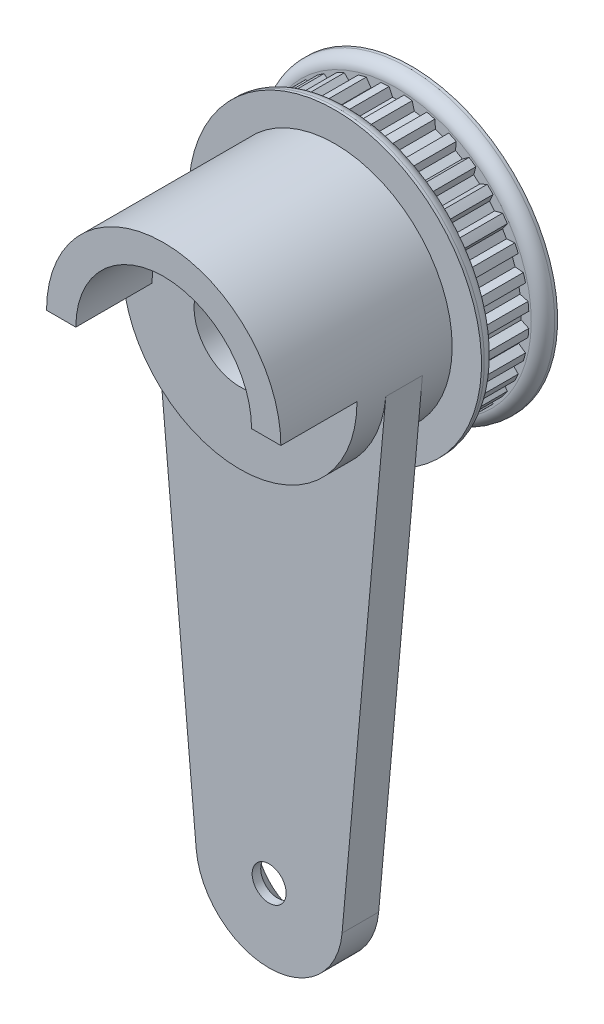
SolidWorks part; units mm, degrees
ref_plane "Front" through (0, 0, 0) normal (0, 0, 1) x (1, 0, 0)
ref_plane "Top" through (0, 0, 0) normal (0, 1, 0) x (1, 0, 0)
ref_plane "Right" through (0, 0, 0) normal (1, 0, 0) x (0, 0, -1)
sketch "Sketch1" plane through (0, 0, 0) normal (0, 0, 1) x (1, 0, 0)
  line L0 (-254, 0) -> (254, 0) construction
  circle A0 centre (0, 0) radius 13.97
  circle A1 centre (0, 0) radius 12.7 construction
  circle A3 centre (0, 0) radius 11.2306 construction
  dimension "D1" = 1.4694
  dimension "D2" = 2.7394
  dimension "D3" = 1.27
extrude "Boss-Extrude1" add sketch "Sketch1" against normal blind 12.7
sketch "Sketch2" plane through (0, 0, 0) normal (1, 0, 0) x (0, 0, -1)
  line L0 (12.7, 0) -> (23.876, 0)
  line L1 (12.7, 0) -> (12.7, 10.668)
  line L2 (12.7, 10.668) -> (23.876, 10.668)
  line L3 (23.876, 10.668) -> (23.876, 0)
  point P5 (23.876, -10.668)
  point P6 (0, -13.97)
  point P7 (12.7, -13.97)
  point P9 (0, 13.97)
revolve "Revolve1" add sketch "Sketch2" angle 360 mid plane about L0 other way angle 360
fillet "Fillet2" radius 0.2794 3 edges at (13.97, 0, -12.7) (13.97, 0, 0) (10.668, 0, -12.7)
sketch "Sketch3" plane through (0, 0, 0) normal (0, 0, 1) x (1, 0, 0)
  line L0 (0, 0) -> (0, 13.97) construction
  line L1 (-4.0817, 11.2144) -> (0, 12.7)
  line L2 (-9.5921, 12.7) -> (9.5921, 12.7) construction
  line L3 (-9.0136, 9.4193) -> (9.0136, 15.9807) construction
  line L4 (-4.0817, 11.2144) -> (0, 0) construction
  line L5 (-9.951, 6.5878) -> (0, 0) construction
  line L6 (-9.951, 6.5878) -> (-3.3571, 16.548) construction
  line L7 (-2.8353, 11.5924) -> (0, 0) construction
  line L8 (-2.8353, 11.5924) -> (0.1182, 12.3148) construction
  arc A0 (-4.0817, 11.2144) -> (-9.951, 6.5878) centre (0, 0) ccw
  circle A1 centre (0, 0) radius 12.7 construction
  circle A2 centre (0, 0) radius 11.9341 construction
  arc A3 (-4.0817, 11.2144) -> (-2.8353, 11.5924) centre (0, 0) cw
  circle A4 centre (0, 0) radius 13.97 construction
  point P6 (0, 12.7)
  dimension "D1" = 4.3437
  dimension "D3" = 11.9451
  dimension "D5" = 3.0406
  dimension "D2" = 7.6014
  dimension "D4" = 1.3031
sketch "Sketch4" plane through (0, 0, 0) normal (0, 0, 1) x (1, 0, 0)
  line L0 (0, 0) -> (0.9934, 12.6218) construction
  line L1 (0.2108, 11.9322) -> (0.2108, 11.2286)
  line L2 (0, 12.7) -> (1.9867, 12.5436) construction
  line L3 (1.6584, 11.8183) -> (1.5483, 11.1234)
  line L4 (0.2108, 11.2286) -> (0, 0) construction
  line L5 (0, 0) -> (0, 13.97) construction
  line L6 (-9.951, 6.5878) -> (-3.3571, 16.548) construction
  line L7 (-9.951, 6.5878) -> (-3.3571, 16.548) construction
  arc A0 (1.5483, 11.1234) -> (0.2108, 11.2286) centre (0, 0) ccw
  arc A1 (0, 12.7) -> (1.9867, 12.5436) centre (0, 0) cw construction
  circle A2 centre (0, 0) radius 12.7 construction
  circle A3 centre (0, 0) radius 11.9341 construction
  circle A4 centre (0, 0) radius 11.2306 construction
  arc A5 (5.9045, 15.8191) -> (-3.3571, 16.548) centre (0, 0) ccw
  spline S0 degree 2 poles (-3.3571, 16.548) (-0.4015, 14.8243) (0.2108, 11.9322) knots 0 0 0 1 1 1
  spline S1 degree 2 poles (5.9045, 15.8191) (2.7156, 14.579) (1.6584, 11.8183) knots 0 0 0 1 1 1
  dimension "D1" = 1.9949
extrude "Cut-Extrude1" cut sketch "Sketch4" against normal through all
fillet "Fillet1" radius 0.5985 2 edges at (1.5483, 11.1234, -6.35) (0.2108, 11.2286, -6.35)
pattern_circular "CirPattern1" count 20 over 360 about axis through (0, 0, -12.7) along (0, 0, 1) of "Cut-Extrude1", "Fillet1"
sketch "Sketch5" plane through (0, 0, 0) normal (0, 0, 1) x (1, 0, 0)
  circle A0 centre (0, 0) radius 6.35
  circle A1 centre (0, 0) radius 6.35 construction
  dimension "Bore Min" = 12.7
  dimension "Bore Max" = 12.7
extrude "Cut-Extrude2" cut sketch "Sketch5" against normal through all
chamfer "Chamfer1" distance 0.5334 angle 45 3 edges at (10.668, 0, -23.876) (6.35, 0, 0) (6.35, 0, -23.876)
sketch "Pitch Dia" plane through (0, 0, 0) normal (0, 0, 1) x (1, 0, 0)
  circle A0 centre (0, 0) radius 12.7 construction
  circle A1 centre (0, 0) radius 12.7 construction
sketch "Sketch7" plane through (0, 0, 0) normal (0, 0, 1) x (1, 0, 0)
  circle A0 centre (0, 0) radius 15.875
  dimension "D1" = 31.75
extrude "Cut-Extrude6" cut sketch "Sketch7" against normal blind 2.54
sketch "Sketch6" plane through (0, 0, -23.876) normal (0, 0, -1) x (-1, 0, 0)
  circle A0 centre (0, 0) radius 15.875
  dimension "D1" = 31.75
extrude "Cut-Extrude7" cut sketch "Sketch6" against normal offset from surface (16.5735 mm away) 4.7625 up to face at (6.35, 0, -2.54)
sketch "Sketch9" plane through (0, 0, -2.54) normal (0, 0, 1) x (1, 0, 0)
  circle A0 centre (0, 0) radius 6.35
  circle A1 centre (0, 0) radius 3.9688
  circle A2 centre (0, 0) radius 6.35 construction
  dimension "D1" = 7.9375
extrude "Boss-Extrude3" add sketch "Sketch9" against normal up to surface (4.7625 mm away) up to face at (6.35, 0, -7.3025)
sketch "Sketch8" plane through (0, 0, -2.54) normal (0, 0, 1) x (1, 0, 0)
  line L0 (10.1192, -0.9099) -> (6.3245, -43.1137)
  line L1 (-6.3245, -43.1137) -> (-10.1192, -0.9099)
  line L2 (0, -42.545) -> (0, 0) construction
  arc A0 (-10.1192, -0.9099) -> (10.1192, -0.9099) centre (0, 0) cw
  arc A1 (6.3245, -43.1137) -> (-6.3245, -43.1137) centre (0, -42.545) cw
  circle A2 centre (0, -42.545) radius 1.4732 construction
  circle A3 centre (0, 0) radius 3.9688
  circle A4 centre (0, 0) radius 3.9688 construction
  dimension "D1" = 10.16
  dimension "D3" = 2.9464
  dimension "D4" = 6.35
  dimension "D2" = 42.545
extrude "Boss-Extrude2" add sketch "Sketch8" along normal blind 3.175
sketch "Sketch10" plane through (0, 0, 0.635) normal (0, 0, 1) x (1, 0, 0)
  circle A0 centre (0, 0) radius 10.16
  circle A1 centre (0, 0) radius 3.9688
  circle A2 centre (0, 0) radius 3.9688 construction
  arc A3 (10.1192, -0.9099) -> (-10.1192, -0.9099) centre (0, 0) ccw construction
extrude "Boss-Extrude4" add sketch "Sketch10" along normal blind 2.54
sketch "Sketch12" plane through (0, 0, 3.175) normal (0, 0, 1) x (1, 0, 0)
  line L0 (-10.16, 0) -> (-7.62, 0)
  line L1 (7.62, 0) -> (10.16, 0)
  arc A0 (-10.16, 0) -> (10.16, 0) centre (0, 0) cw
  circle A2 centre (0, 0) radius 10.16 construction
  arc A3 (10.1192, -0.9099) -> (-10.1192, -0.9099) centre (0, 0) ccw construction
  arc A4 (-7.62, 0) -> (7.62, 0) centre (0, 0) cw
  dimension "D1" = 2.54
extrude "Boss-Extrude5" add sketch "Sketch12" along normal blind 6.604
sketch "Sketch13" plane through (0, 0, -7.3025) normal (0, 0, -1) x (-1, 0, 0)
  circle A0 centre (0, 0) radius 15.875
  dimension "D1" = 31.75
extrude "Cut-Extrude8" cut sketch "Sketch13" against normal up to surface (4.7625 mm away) up to face at (-0.6308, -12.5539, -2.54)
sketch "Sketch18" plane through (0, 0, -2.54) normal (0, 0, -1) x (-1, 0, 0)
  circle A0 centre (0, 0) radius 10.16
  arc A1 (10.1192, -0.9099) -> (-10.1192, -0.9099) centre (0, 0) ccw construction
  circle A2 centre (0, 0) radius 3.9688
  circle A3 centre (0, 0) radius 3.9688 construction
extrude "Boss-Extrude10" add sketch "Sketch18" along normal blind 2.54
sketch "Sketch16" plane through (0, 0, -5.08) normal (0, 0, -1) x (-1, 0, 0)
  circle A0 centre (0, 0) radius 12.7
  circle A1 centre (0, 0) radius 3.9688
  circle A2 centre (0, 0) radius 3.9688 construction
  dimension "D1" = 25.4
extrude "Boss-Extrude8" add sketch "Sketch16" along normal blind 1.27
sketch "Sketch14" plane through (0, 0, -6.35) normal (0, 0, -1) x (-1, 0, 0)
  line L120 (10.5919, 2.2117) -> (10.7096, 1.5443)
  line L121 (11.1831, 2.6256) -> (10.5919, 2.2117)
  line L122 (10.2788, 3.3805) -> (10.9976, 3.3177)
  line L123 (10.047, 4.0174) -> (10.2788, 3.3805)
  line L124 (10.5572, 4.5277) -> (10.047, 4.0174)
  line L125 (9.5356, 5.1141) -> (10.2544, 5.177)
  line L126 (9.1967, 5.701) -> (9.5356, 5.1141)
  line L127 (9.6106, 6.2921) -> (9.1967, 5.701)
  line L128 (8.5027, 6.6922) -> (9.1997, 6.879)
  line L129 (8.067, 7.2114) -> (8.5027, 6.6922)
  line L130 (8.372, 7.8654) -> (8.067, 7.2114)
  line L131 (7.2114, 8.067) -> (7.8654, 8.372)
  line L132 (6.6922, 8.5027) -> (7.2114, 8.067)
  line L133 (6.879, 9.1997) -> (6.6922, 8.5027)
  line L134 (5.701, 9.1967) -> (6.2921, 9.6106)
  line L135 (5.1141, 9.5356) -> (5.701, 9.1967)
  line L136 (5.177, 10.2544) -> (5.1141, 9.5356)
  line L137 (4.0174, 10.047) -> (4.5277, 10.5572)
  line L138 (3.3805, 10.2788) -> (4.0174, 10.047)
  line L139 (3.3177, 10.9976) -> (3.3805, 10.2788)
  line L140 (2.2117, 10.5919) -> (2.6256, 11.1831)
  line L141 (1.5443, 10.7096) -> (2.2117, 10.5919)
  line L142 (1.3575, 11.4067) -> (1.5443, 10.7096)
  line L143 (0.3389, 10.8151) -> (0.6438, 11.4691)
  line L144 (-0.3389, 10.8151) -> (0.3389, 10.8151)
  line L145 (-0.6438, 11.4691) -> (-0.3389, 10.8151)
  line L146 (-1.5443, 10.7096) -> (-1.3575, 11.4067)
  line L147 (-2.2117, 10.5919) -> (-1.5443, 10.7096)
  line L148 (-2.6256, 11.1831) -> (-2.2117, 10.5919)
  line L149 (-3.3805, 10.2788) -> (-3.3177, 10.9976)
  line L150 (-4.0174, 10.047) -> (-3.3805, 10.2788)
  line L151 (-4.5277, 10.5572) -> (-4.0174, 10.047)
  line L152 (-5.1141, 9.5356) -> (-5.177, 10.2544)
  line L153 (-5.701, 9.1967) -> (-5.1141, 9.5356)
  line L154 (-6.2921, 9.6106) -> (-5.701, 9.1967)
  line L155 (-6.6922, 8.5027) -> (-6.879, 9.1997)
  line L156 (-7.2114, 8.067) -> (-6.6922, 8.5027)
  line L157 (-7.8654, 8.372) -> (-7.2114, 8.067)
  line L158 (-8.067, 7.2114) -> (-8.372, 7.8654)
  line L159 (-8.5027, 6.6922) -> (-8.067, 7.2114)
  line L160 (-9.1997, 6.879) -> (-8.5027, 6.6922)
  line L161 (-9.1967, 5.701) -> (-9.6106, 6.2921)
  line L162 (-9.5356, 5.1141) -> (-9.1967, 5.701)
  line L163 (-10.2544, 5.177) -> (-9.5356, 5.1141)
  line L164 (-10.047, 4.0174) -> (-10.5572, 4.5277)
  line L165 (-10.2788, 3.3805) -> (-10.047, 4.0174)
  line L166 (-10.9976, 3.3177) -> (-10.2788, 3.3805)
  line L167 (-10.5919, 2.2117) -> (-11.1831, 2.6256)
  line L168 (-10.7096, 1.5443) -> (-10.5919, 2.2117)
  line L169 (-11.4067, 1.3575) -> (-10.7096, 1.5443)
  line L170 (-10.8151, 0.3389) -> (-11.4691, 0.6438)
  line L171 (-10.8151, -0.3389) -> (-10.8151, 0.3389)
  line L172 (-11.4691, -0.6438) -> (-10.8151, -0.3389)
  line L173 (-10.7096, -1.5443) -> (-11.4067, -1.3575)
  line L174 (-10.5919, -2.2117) -> (-10.7096, -1.5443)
  line L175 (-11.1831, -2.6256) -> (-10.5919, -2.2117)
  line L176 (-10.2788, -3.3805) -> (-10.9976, -3.3177)
  line L177 (-10.047, -4.0174) -> (-10.2788, -3.3805)
  line L178 (-10.5572, -4.5277) -> (-10.047, -4.0174)
  line L179 (-9.5356, -5.1141) -> (-10.2544, -5.177)
  line L180 (-9.1967, -5.701) -> (-9.5356, -5.1141)
  line L181 (-9.6106, -6.2921) -> (-9.1967, -5.701)
  line L182 (-8.5027, -6.6922) -> (-9.1997, -6.879)
  line L183 (-8.067, -7.2114) -> (-8.5027, -6.6922)
  line L184 (-8.372, -7.8654) -> (-8.067, -7.2114)
  line L185 (-7.2114, -8.067) -> (-7.8654, -8.372)
  line L186 (-6.6922, -8.5027) -> (-7.2114, -8.067)
  line L187 (-6.879, -9.1997) -> (-6.6922, -8.5027)
  line L188 (-5.701, -9.1967) -> (-6.2921, -9.6106)
  line L189 (-5.1141, -9.5356) -> (-5.701, -9.1967)
  line L190 (-5.177, -10.2544) -> (-5.1141, -9.5356)
  line L191 (-4.0174, -10.047) -> (-4.5277, -10.5572)
  line L192 (-3.3805, -10.2788) -> (-4.0174, -10.047)
  line L193 (-3.3177, -10.9976) -> (-3.3805, -10.2788)
  line L194 (-2.2117, -10.5919) -> (-2.6256, -11.1831)
  line L195 (-1.5443, -10.7096) -> (-2.2117, -10.5919)
  line L196 (-1.3575, -11.4067) -> (-1.5443, -10.7096)
  line L197 (-0.3389, -10.8151) -> (-0.6438, -11.4691)
  line L198 (0.3389, -10.8151) -> (-0.3389, -10.8151)
  line L199 (0.6438, -11.4691) -> (0.3389, -10.8151)
  line L200 (1.5443, -10.7096) -> (1.3575, -11.4067)
  line L201 (2.2117, -10.5919) -> (1.5443, -10.7096)
  line L202 (2.6256, -11.1831) -> (2.2117, -10.5919)
  line L203 (3.3805, -10.2788) -> (3.3177, -10.9976)
  line L204 (4.0174, -10.047) -> (3.3805, -10.2788)
  line L205 (4.5277, -10.5572) -> (4.0174, -10.047)
  line L206 (5.1141, -9.5356) -> (5.177, -10.2544)
  line L207 (5.701, -9.1967) -> (5.1141, -9.5356)
  line L208 (6.2921, -9.6106) -> (5.701, -9.1967)
  line L209 (6.6922, -8.5027) -> (6.879, -9.1997)
  line L210 (7.2114, -8.067) -> (6.6922, -8.5027)
  line L211 (7.8654, -8.372) -> (7.2114, -8.067)
  line L212 (8.067, -7.2114) -> (8.372, -7.8654)
  line L213 (8.5027, -6.6922) -> (8.067, -7.2114)
  line L214 (9.1997, -6.879) -> (8.5027, -6.6922)
  line L215 (9.1967, -5.701) -> (9.6106, -6.2921)
  line L216 (9.5356, -5.1141) -> (9.1967, -5.701)
  line L217 (10.2544, -5.177) -> (9.5356, -5.1141)
  line L218 (10.047, -4.0174) -> (10.5572, -4.5277)
  line L219 (10.2788, -3.3805) -> (10.047, -4.0174)
  line L220 (10.9976, -3.3177) -> (10.2788, -3.3805)
  line L221 (10.5919, -2.2117) -> (11.1831, -2.6256)
  line L222 (10.7096, -1.5443) -> (10.5919, -2.2117)
  line L223 (11.4067, -1.3575) -> (10.7096, -1.5443)
  line L224 (10.8151, -0.3389) -> (11.4691, -0.6438)
  line L225 (10.8151, 0.3389) -> (10.8151, -0.3389)
  line L226 (11.4691, 0.6438) -> (10.8151, 0.3389)
  line L227 (10.7096, 1.5443) -> (11.4067, 1.3575)
  arc A43 (11.1831, 2.6256) -> (10.9976, 3.3177) centre (0, 0) ccw
  arc A44 (10.5572, 4.5277) -> (10.2544, 5.177) centre (0, 0) ccw
  arc A45 (9.6106, 6.2921) -> (9.1997, 6.879) centre (0, 0) ccw
  arc A46 (8.372, 7.8654) -> (7.8654, 8.372) centre (0, 0) ccw
  arc A47 (6.879, 9.1997) -> (6.2921, 9.6106) centre (0, 0) ccw
  arc A48 (5.177, 10.2544) -> (4.5277, 10.5572) centre (0, 0) ccw
  arc A49 (3.3177, 10.9976) -> (2.6256, 11.1831) centre (0, 0) ccw
  arc A50 (1.3575, 11.4067) -> (0.6438, 11.4691) centre (0, 0) ccw
  arc A51 (-0.6438, 11.4691) -> (-1.3575, 11.4067) centre (0, 0) ccw
  arc A52 (-2.6256, 11.1831) -> (-3.3177, 10.9976) centre (0, 0) ccw
  arc A53 (-4.5277, 10.5572) -> (-5.177, 10.2544) centre (0, 0) ccw
  arc A54 (-6.2921, 9.6106) -> (-6.879, 9.1997) centre (0, 0) ccw
  arc A55 (-7.8654, 8.372) -> (-8.372, 7.8654) centre (0, 0) ccw
  arc A56 (-9.1997, 6.879) -> (-9.6106, 6.2921) centre (0, 0) ccw
  arc A57 (-10.2544, 5.177) -> (-10.5572, 4.5277) centre (0, 0) ccw
  arc A58 (-10.9976, 3.3177) -> (-11.1831, 2.6256) centre (0, 0) ccw
  arc A59 (-11.4067, 1.3575) -> (-11.4691, 0.6438) centre (0, 0) ccw
  arc A60 (-11.4691, -0.6438) -> (-11.4067, -1.3575) centre (0, 0) ccw
  arc A61 (-11.1831, -2.6256) -> (-10.9976, -3.3177) centre (0, 0) ccw
  arc A62 (-10.5572, -4.5277) -> (-10.2544, -5.177) centre (0, 0) ccw
  arc A63 (-9.6106, -6.2921) -> (-9.1997, -6.879) centre (0, 0) ccw
  arc A64 (-8.372, -7.8654) -> (-7.8654, -8.372) centre (0, 0) ccw
  arc A65 (-6.879, -9.1997) -> (-6.2921, -9.6106) centre (0, 0) ccw
  arc A66 (-5.177, -10.2544) -> (-4.5277, -10.5572) centre (0, 0) ccw
  arc A67 (-3.3177, -10.9976) -> (-2.6256, -11.1831) centre (0, 0) ccw
  arc A68 (-1.3575, -11.4067) -> (-0.6438, -11.4691) centre (0, 0) ccw
  arc A69 (0.6438, -11.4691) -> (1.3575, -11.4067) centre (0, 0) ccw
  arc A70 (2.6256, -11.1831) -> (3.3177, -10.9976) centre (0, 0) ccw
  arc A71 (4.5277, -10.5572) -> (5.177, -10.2544) centre (0, 0) ccw
  arc A72 (6.2921, -9.6106) -> (6.879, -9.1997) centre (0, 0) ccw
  arc A73 (7.8654, -8.372) -> (8.372, -7.8654) centre (0, 0) ccw
  arc A74 (9.1997, -6.879) -> (9.6106, -6.2921) centre (0, 0) ccw
  arc A75 (10.2544, -5.177) -> (10.5572, -4.5277) centre (0, 0) ccw
  arc A76 (10.9976, -3.3177) -> (11.1831, -2.6256) centre (0, 0) ccw
  arc A77 (11.4067, -1.3575) -> (11.4691, -0.6438) centre (0, 0) ccw
  arc A78 (11.4691, 0.6438) -> (11.4067, 1.3575) centre (0, 0) ccw
  circle A79 centre (0, 0) radius 3.175 construction
  circle A80 centre (0, 0) radius 3.9688
  circle A81 centre (0, 0) radius 3.9688 construction
extrude "Boss-Extrude6" add sketch "Sketch14" along normal blind 4.064
sketch "Sketch15" plane through (0, 0, -10.414) normal (0, 0, -1) x (-1, 0, 0)
  circle A0 centre (0, 0) radius 3.9688
  circle A1 centre (0, 0) radius 12.7
  circle A3 centre (0, 0) radius 3.9688 construction
  dimension "1" = 25.4
extrude "Boss-Extrude7" add sketch "Sketch15" along normal blind 1.27
fillet "Fillet3" radius 1.016 2 edges at (-12.7, 0, -10.414) (-12.7, 0, -6.35)
hole_wizard "CSK for #4 Flat Head Machine Screw (100)1" positions "Sketch19" profile "Sketch20" countersink size "#4" standard "ANSI Inch" end condition through all
sketch "Sketch19" plane through (0, 0, -2.54) normal (0, 0, -1) x (-1, 0, 0)
  point P0 (0, -42.545)
sketch "Sketch20" plane through (0, -42.545, -2.54) normal (1, 0, 0) x (0, 1, 0)
  line L0 (0, 0) -> (0, 12.319)
  line L1 (0, 12.319) -> (1.4732, 12.319)
  line L2 (1.4732, 12.319) -> (1.4732, 2.4316)
  line L3 (1.4732, 2.4316) -> (4.371, 0)
  line L5 (4.371, 0) -> (0, 0)
  line L6 (-1.4732, 2.4316) -> (-4.371, 0) construction
  line L11 (0, -6.35) -> (0, 107.95) construction
  dimension "Thru Hole Dia." = 2.9464
  dimension "Thru Hole Depth" = 12.319
  dimension "Near C'Sink Dia." = 8.742
  dimension "Near C'Sink Angle" = 100
equation "\"D1@Boss-Extrude1\" = \"Face Wd@Sketch2\""
equation "\"D2@Sketch3\" = \"D1@Sketch3\"*1.75"
equation "\"D3@Sketch3\" = \"D1@Sketch3\"+\"D2@Sketch3\""
equation "\"D4@Sketch3\" = \"D1@Sketch3\"*.3"
equation "\"D5@Sketch3\" = \"D1@Sketch3\"-\"D4@Sketch3\""
equation "\"D1@Sketch4\" = 1.5708/(\"Number of Teeth@Sketch1\"/\"Ptich Dia@Sketch1\")"
equation "\"D1@Chamfer1\" = \"B Hub Dia@Sketch2\"*.025"
equation "\"D1@CirPattern1\" = \"Number of Teeth@Sketch1\""
equation "\"D1@Fillet1\" = \"D1@Sketch4\"*.3"
equation "\"D1@Fillet2\" = \"OD@Sketch1\"*.01"
equation "\"D1@Sketch1\" = 1.157/(\"Number of Teeth@Sketch1\"/\"Ptich Dia@Sketch1\")"
